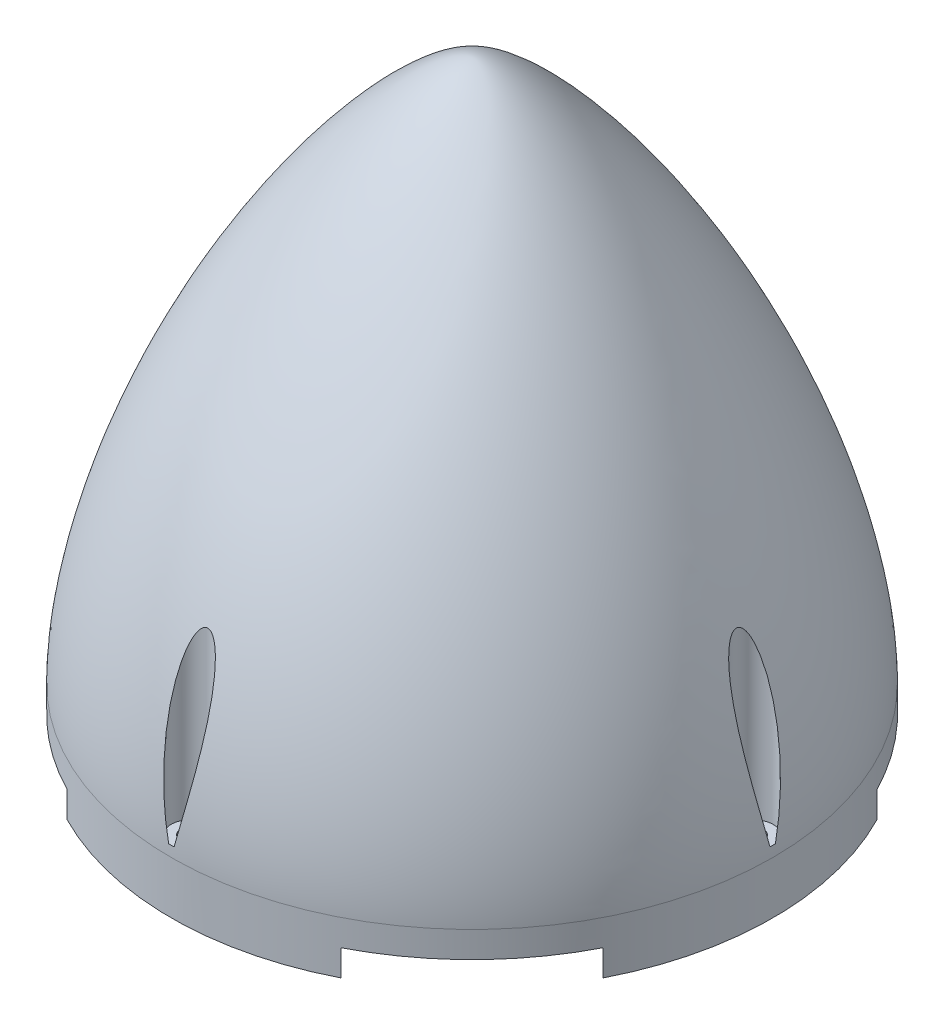
SolidWorks part; units mm, degrees
ref_plane "Front Plane" through (0, 0, 0) normal (0, 0, 1) x (1, 0, 0)
ref_plane "Top Plane" through (0, 0, 0) normal (0, 1, 0) x (1, 0, 0)
ref_plane "Right Plane" through (0, 0, 0) normal (1, 0, 0) x (0, 0, -1)
sketch "Sketch1" plane through (0, 0, 0) normal (0, 0, 1) x (1, 0, 0)
  line L0 (57.5, 0) -> (57.5, 22.4869) construction
  line L1 (57.5, 22.4869) -> (44.5234, 66.8228) construction
  line L2 (44.5234, 66.8228) -> (11.0902, 103.626) construction
  line L3 (11.0902, 103.626) -> (0, 103.626) construction
  line L4 (47.5, 0) -> (47.5, 22.4869) construction
  line L5 (47.5, 22.4869) -> (34.5234, 66.8228) construction
  line L6 (34.5234, 66.8228) -> (10.1745, 93.626) construction
  line L7 (10.1745, 93.626) -> (0, 93.626) construction
  line L9 (47.5, 0) -> (57.5, 0)
  line L10 (0, 93.626) -> (0, 103.626)
  line L11 (0, 0) -> (0, 52.5) construction
  line L12 (57.5, 22.4869) -> (44.5234, 66.8228) construction
  line L13 (47.5, 22.4869) -> (34.5234, 66.8228) construction
  line L14 (44.5234, 66.8228) -> (11.0902, 103.626) construction
  line L15 (34.5234, 66.8228) -> (10.1745, 93.626) construction
  line L16 (57.5, 22.4869) -> (47.5, 22.4869) construction
  spline S0 degree 4 poles (57.5, 0) (57.5, 22.4869) (44.5234, 66.8228) (11.0902, 103.626) (0, 103.626) knots 0 0 0 0 0 1 1 1 1 1
  spline S1 degree 4 poles (47.5, 0) (47.5, 22.4869) (34.5234, 66.8228) (10.1745, 93.626) (0, 93.626) knots 0 0 0 0 0 1 1 1 1 1
  dimension "D3" = 10
  dimension "D1" = 10
  dimension "D2" = 57.5
  dimension "D4" = 10
  dimension "D5" = 10
  dimension "D6" = 10
revolve "Revolve2" add sketch "Sketch1" angle 360 about L11
sketch "Sketch3" plane through (0, 0, 0) normal (0, -1, 0) x (1, 0, 0)
  circle A0 centre (0, 0) radius 57.5
  dimension "D1" = 115
extrude "Boss-Extrude1" add sketch "Sketch3" along normal blind 5
sketch "Sketch9" plane through (0, -5, 0) normal (0, -1, 0) x (1, 0, 0)
  line L0 (0, -25) -> (-26.1895, -51.1895)
  line L1 (0, -25) -> (26.1895, -51.1895)
  line L2 (26.1895, -51.1895) -> (-26.1895, -51.1895) construction
  arc A0 (26.1895, -51.1895) -> (-26.1895, -51.1895) centre (0, 0) cw
  circle A1 centre (0, 0) radius 57.5 construction
  circle M2 centre (0, 0) radius 57.5
  dimension "D1" = 25
  dimension "D2" = 90
extrude "Boss-Extrude2" add sketch "Sketch9" along normal blind 5 contours M2 | L2 L1 L0 region at (0, -5, -42.4596) region at (0, -5, -53.7259)
pattern_circular "CirPattern2" count 4 over 360 about axis through (0, -5, 0) along (0, -1, 0) of "Boss-Extrude2"
sketch "Sketch7" plane through (0, -10, 0) normal (0, -1, 0) x (1, 0, 0)
  circle A0 centre (-54, 0) radius 1.75
  dimension "D1" = 3.5
  dimension "D2" = 54
extrude "Cut-Extrude1" cut sketch "Sketch7" against normal blind 12
sketch "Sketch8" plane through (0, 2, 0) normal (0, -1, 0) x (1, 0, 0)
  circle A0 centre (-54, 0) radius 3.5
  dimension "D1" = 7
extrude "Cut-Extrude2" cut sketch "Sketch8" against normal through all
pattern_circular "CirPattern1" count 4 over 360 about axis through (0, 0, 0) along (0, -1, 0) of "Cut-Extrude2", "Cut-Extrude1"
